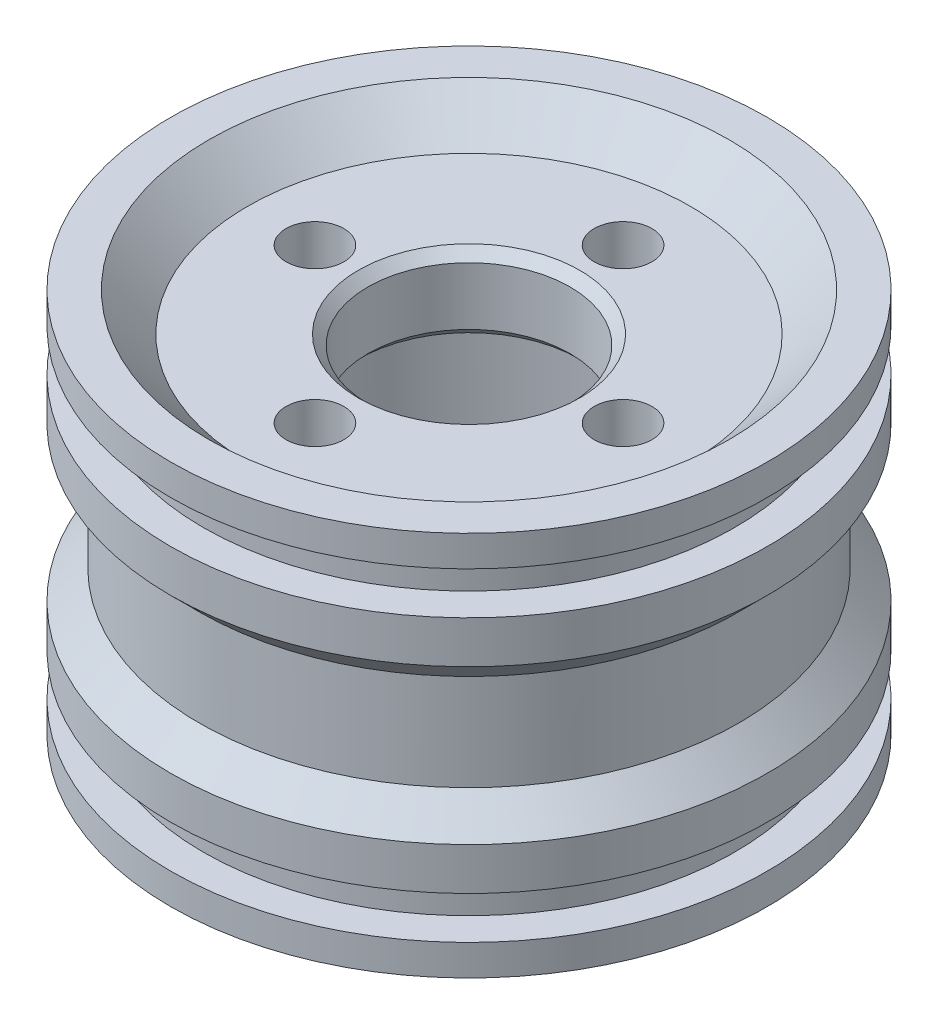
SolidWorks part; units mm, degrees
ref_plane "前视基准面" through (0, 0, 0) normal (0, 0, 1) x (1, 0, 0)
ref_plane "上视基准面" through (0, 0, 0) normal (0, 1, 0) x (1, 0, 0)
ref_plane "右视基准面" through (0, 0, 0) normal (1, 0, 0) x (0, 0, -1)
other "Configuration Table"
sketch "草图1" plane through (0, 0, 0) normal (0, 1, 0) x (1, 0, 0)
  circle A0 centre (0, 0) radius 15.5
  dimension "D1" = 31
extrude "凸台-拉伸1" add sketch "草图1" along normal mid plane 20
sketch "草图2" plane through (0, 0, 0) normal (0, 0, 1) x (1, 0, 0)
  line L0 (15.5, -10) -> (15.5, 10) construction
  line L1 (15.5, 8.4) -> (0, 8.4) construction
  line L2 (15.5, 8.4) -> (15.5, 6.2) construction
  line L3 (15.5, 6.2) -> (0, 6.2) construction
  line L4 (0, 8.4) -> (0, 6.2) construction
  line L5 (15.5, 10) -> (-15.5, 10) construction
  line L7 (15.5, 8.4) -> (13.8, 8.4)
  line L8 (15.5, 8.4) -> (15.5, 6.2)
  line L9 (15.5, 6.2) -> (13.8, 6.2)
  line L10 (13.8, 8.4) -> (13.8, 6.2)
  dimension "D1" = 2.2
  dimension "D2" = 1.6
  dimension "D3" = 1.7
revolve "切除-旋转1" cut sketch "草图2" angle 360 about L4
mirror "镜向1" about plane through (0, 0, 0) normal (0, 1, 0) of "切除-旋转1"
sketch "草图4" plane through (0, -10, 0) normal (0, -1, 0) x (1, 0, 0)
  circle A0 centre (0, 0) radius 11.5
  dimension "D1" = 23
extrude "切除-拉伸1" cut sketch "草图4" against normal blind 14
sketch "草图5" plane through (0, 10, 0) normal (0, 1, 0) x (1, 0, 0)
  circle A0 centre (0, 0) radius 5.25
  dimension "D1" = 10.5
extrude "切除-拉伸2" cut sketch "草图5" against normal blind 15 contours A0 region at (0, 10, 0)
chamfer "倒角1" distance 2 angle 45 1 edges at (0, -10, -11.5)
sketch "草图6" plane through (0, 10, 0) normal (0, 1, 0) x (1, 0, 0)
  circle A0 centre (0, 0) radius 5
  circle A1 centre (0, 0) radius 11.5
  dimension "D1" = 23
  dimension "D2" = 10
extrude "切除-拉伸3" cut sketch "草图6" against normal blind 2
chamfer "倒角2" distance 2 angle 45 1 edges at (0, 10, 11.5)
ref_axis "基准轴1" through (0, 4, 0) along (0, 1, 0)
sketch "草图7" plane through (0, 0, 0) normal (1, 0, 0) x (0, 0, -1)
  line L0 (15.5, -6.2) -> (15.5, 6.2) construction
  line L1 (14, -4) -> (15.5, -4)
  line L2 (14, -4) -> (14, 4)
  line L3 (14, 4) -> (15.5, 4)
  line L4 (15.5, -4) -> (15.5, 4)
  line L5 (14, -4) -> (15.5, 4) construction
  line L6 (14, 4) -> (15.5, -4) construction
  point P0 (14.75, 0)
  dimension "D1" = 1.5
  dimension "D2" = 8
sketch "草图8" plane through (0, 4, 0) normal (0, -1, 0) x (1, 0, 0)
  circle A0 centre (-8, 0) radius 1.5
  dimension "D1" = 3
  dimension "D2" = 8
extrude "切除-拉伸4" cut sketch "草图8" against normal blind 10
pattern_circular "阵列(圆周)1" count 4 over 360 about axis through (0, 4, 0) along (0, 1, 0) of "切除-拉伸4"
revolve "切除-旋转2" cut sketch "草图7" angle 360 about axis through (0, 4, 0) along (0, 1, 0)
chamfer "倒角5" distance 1.5 angle 45 2 edges at (0, 4, -14) (0, -4, -14)
chamfer "倒角4" distance 0.5 angle 45 3 edges at (0, 4, -11.5) (0, 8, 5.25) (0, 4, -5.25)
sketch "草图9" plane through (0, 0, 0) normal (0, 0, 1) x (1, 0, 0)
  line L0 (15.5, 10) -> (-15.5, 10) construction
  circle A0 centre (0, 3) radius 1.5
  dimension "D2" = 3
  dimension "D1" = 7
